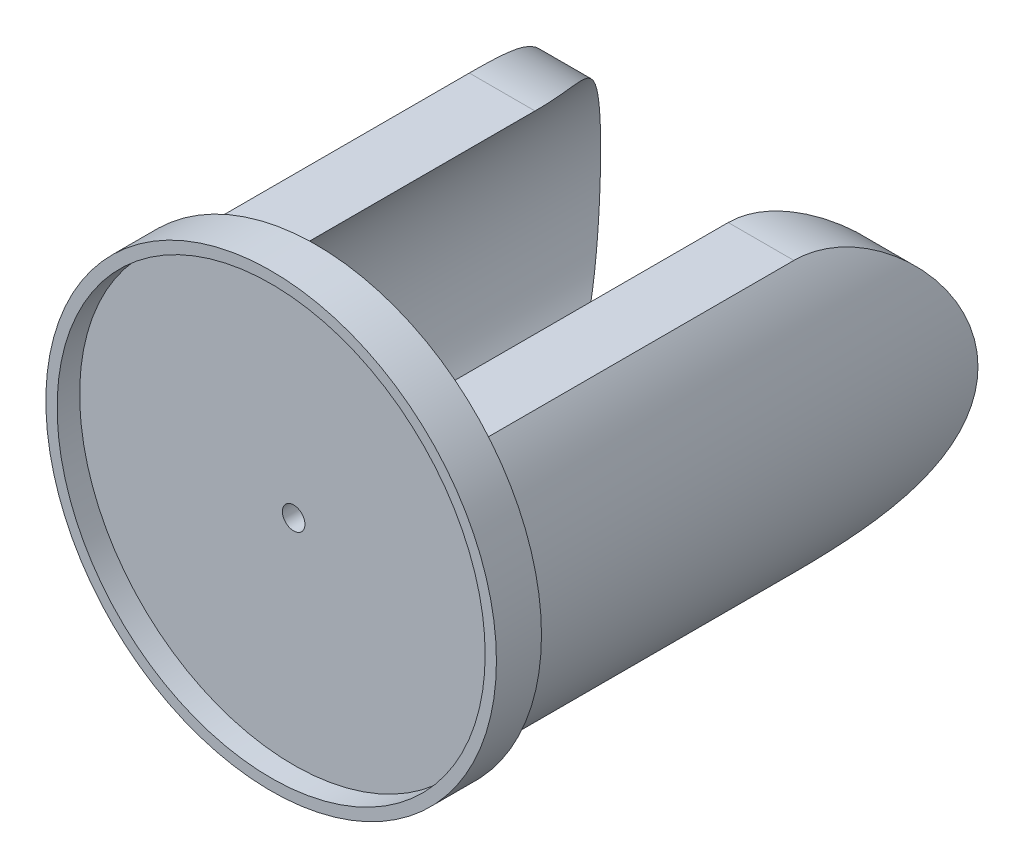
SolidWorks part; units mm, degrees
ref_plane "Plan de face" through (0, 0, 0) normal (0, 0, 1) x (1, 0, 0)
ref_plane "Plan de dessus" through (0, 0, 0) normal (0, 1, 0) x (1, 0, 0)
ref_plane "Plan de droite" through (0, 0, 0) normal (1, 0, 0) x (0, 0, -1)
sketch "Esquisse1" plane through (0, 0, 0) normal (0, 0, 1) x (1, 0, 0)
  line L0 (0, 0) -> (0, 50)
  line L1 (0, 50) -> (0, -50)
  line L2 (-50, 0) -> (50, 0)
  circle A0 centre (0, 0) radius 50
  circle A1 centre (0, 0) radius 47.5
  dimension "D1" = 100
  dimension "D2" = 95
extrude "Boss.-Extru.1" add sketch "Esquisse1" along normal blind 10 contours A0
sketch "Esquisse2" plane through (0, 0, 10) normal (0, 0, 1) x (1, 0, 0)
  circle A0 centre (0, 0) radius 47.5
  dimension "D1" = 95
extrude "Enlèv. mat.-Extru.1" cut sketch "Esquisse2" against normal blind 5
sketch "Esquisse3" plane through (0, 0, 0) normal (0, 0, -1) x (-1, 0, 0)
  circle A0 centre (0, 0) radius 2.5
  dimension "D1" = 5
extrude "Enlèv. mat.-Extru.2" cut sketch "Esquisse3" against normal blind 16
sketch "Esquisse4" plane through (0, 0, 0) normal (0, 0, -1) x (-1, 0, 0)
  circle A0 centre (0, 0) radius 35
  dimension "D1" = 70
extrude "Boss.-Extru.2" add sketch "Esquisse4" along normal blind 7
sketch "Esquisse5" plane through (0, 0, 0) normal (0, 0, -1) x (-1, 0, 0)
  line L0 (0, 0) -> (50, 0)
  line L1 (50, 0) -> (-50, 0)
  line L2 (0, 50) -> (0, -50)
  line L3 (50, 0) -> (50, 30)
  line L4 (50, 30) -> (50, -30)
  line L5 (50, 30) -> (21.4421, 30)
  line L6 (50, -30) -> (21.4421, -30)
  line L7 (-50, 30) -> (-50, -30)
  line L8 (-50, 0) -> (-50, 30)
  line L9 (-50, -30) -> (-21.4421, -30)
  line L10 (-50, 30) -> (-21.4421, 30)
  circle A0 centre (0, 0) radius 46.875
  circle A1 centre (0, 0) radius 36.875
  circle A2 centre (0, 0) radius 50 construction
  dimension "D1" = 10
  dimension "D2" = 73.75
  dimension "D3" = 30
  dimension "D4" = 60
extrude "Boss.-Extru.3" add sketch "Esquisse5" along normal blind 100 contours A1 L10 A0 L1 | A1 L1 A0 L9 | A1 L1 A0 L5 | A1 L6 A0 L1 region at (-37.4359, 15.8827, 0) region at (-37.4359, -15.8827, 0) region at (37.4359, -15.8827, 0) region at (37.4359, 15.8827, 0)
fillet "Congé1" radius 30 4 edges at (28.7299, 30, -100) (-28.7299, 30, -100) (28.7299, -30, -100) (-28.7299, -30, -100)
